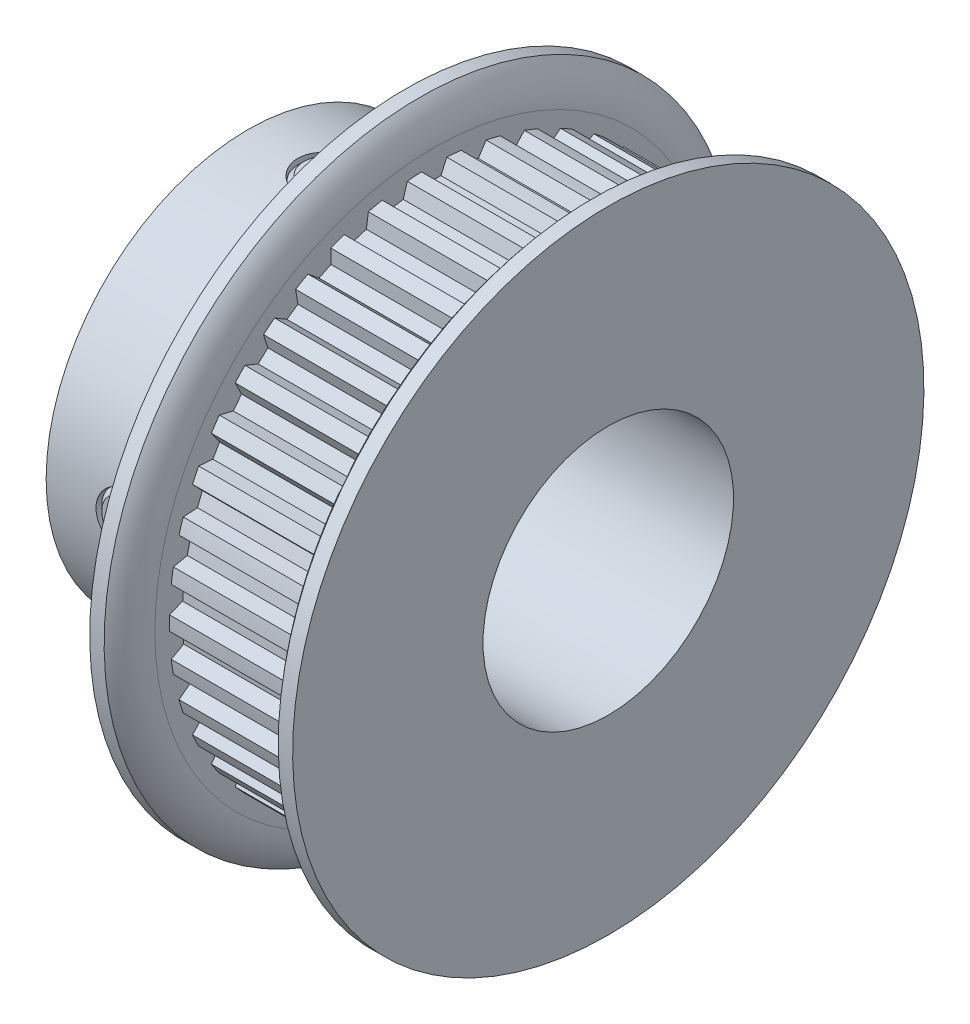
SolidWorks part; units mm, degrees
ref_plane "Front Plane" through (0, 0, 0) normal (0, 0, 1) x (1, 0, 0)
ref_plane "Top Plane" through (0, 0, 0) normal (0, 1, 0) x (1, 0, 0)
ref_plane "Right Plane" through (0, 0, 0) normal (1, 0, 0) x (0, 0, -1)
sketch "Sketch2" plane through (0, 0, 0) normal (1, 0, 0) x (0, 0, -1)
  line L3 (0, 0) -> (0, 12.7635) construction
  line L6 (0, -13.2715) -> (0, -13.589) construction
  line L7 (-0.5715, 13.2592) -> (-0.3383, 12.759)
  line L8 (0.5715, 13.2592) -> (0.3383, 12.759)
  line L9 (-0.5715, 13.2592) -> (-0.6441, 13.4148)
  line L10 (0.5715, 13.2592) -> (0.6441, 13.4148)
  line L12 (-0.3383, 12.759) -> (0.3383, 12.759)
  line L14 (0, 13.2715) -> (0, 13.589) construction
  line L15 (0, 0) -> (0, -1.143) construction
  circle A0 centre (0, 0) radius 13.589 construction
  circle A1 centre (0, 0) radius 12.7635 construction
  circle A2 centre (0, 0) radius 13.2715 construction
  arc A7 (0.6441, 13.4148) -> (-0.6441, 13.4148) centre (0, 0) ccw
  point P5 (0, 13.4303)
  dimension "D3" = 0.3175
  dimension "D1" = 50
sketch "Sketch1" plane through (0, 0, 0) normal (0, 0, 1) x (1, 0, 0)
  line L0 (-9.1313, 0) -> (9.1313, 0) construction
  line L1 (-9.1313, 6.35) -> (9.1313, 6.35)
  line L2 (-9.1313, 6.35) -> (-9.1313, 10.2362)
  line L3 (-1.1557, 16.002) -> (-0.4254, 16.002)
  line L4 (0.3048, 13.589) -> (0.3048, 14.1605)
  line L5 (0.3048, 14.732) -> (0.3048, 13.589) construction
  line L6 (0.3048, 13.589) -> (7.6708, 13.589)
  line L7 (7.6708, 13.589) -> (7.6708, 14.1605)
  line L8 (7.6708, 13.589) -> (9.1313, 13.589) construction
  line L9 (8.4011, 16.002) -> (9.1313, 16.002)
  line L10 (9.1313, 16.002) -> (9.1313, 6.35)
  line L11 (8.4011, 13.589) -> (8.4011, 16.002) construction
  line L12 (-5.1435, 10.2362) -> (-5.1435, 6.35) construction
  line L13 (-1.1557, 16.002) -> (-1.1557, 10.2362)
  line L14 (-1.1557, 10.2362) -> (-9.1313, 10.2362)
  arc A0 (7.6708, 14.1605) -> (8.4011, 16.002) centre (10.3578, 14.1605) cw
  arc A1 (0.3048, 14.1605) -> (-0.4254, 16.002) centre (-2.3822, 14.1605) ccw
  dimension "Bore Size" = 12.7
  dimension "Overall Width" = 18.2626
  dimension "Inside Width" = 7.366
  dimension "OD" = 32.004
  dimension "D2" = 27.178
  dimension "D3" = 1.143
  dimension "D4" = 0.5715
  dimension "Outside Width" = 10.287
revolve "Revolve1" add sketch "Sketch1" angle 360 mid plane about L0
sketch "Sketch4" plane through (0.3048, 0, 0) normal (1, 0, 0) x (0, 0, -1)
  circle A0 centre (0, 0) radius 13.4303
  circle A2 centre (0, 0) radius 13.589
  circle A3 centre (0, 0) radius 13.589 construction
extrude "Cut-Extrude2" cut sketch "Sketch4" along normal up to surface (7.366 mm away) up to face at (7.6708, -13.589, 0)
sketch "Sketch3" plane through (0.3048, 0, 0) normal (1, 0, 0) x (0, 0, -1)
  line L2 (-0.5715, 13.2592) -> (-0.3383, 12.759) construction
  line L3 (-0.3383, 12.759) -> (0.3383, 12.759) construction
  line L4 (0.5715, 13.2592) -> (0.3383, 12.759) construction
  line L5 (-0.6441, 13.4148) -> (-0.3383, 12.759)
  line L6 (-0.3383, 12.759) -> (0.3383, 12.759)
  line L7 (0.6441, 13.4148) -> (0.3383, 12.759)
  arc A1 (0.6441, 13.4148) -> (-0.6441, 13.4148) centre (0, 0) ccw construction
  arc A2 (0.6441, 13.4148) -> (-0.6441, 13.4148) centre (0, 0) ccw
extrude "Cut-Extrude1" cut sketch "Sketch3" along normal up to surface (7.366 mm away) up to face at (7.6708, -14.1605, 0)
pattern_circular "CirPattern1" count 42 over 360 of "Cut-Extrude1"
sketch "Sketch5" plane through (0, 0, 0) normal (0, 0, 1) x (1, 0, 0)
  line L1 (7.6708, 14.1605) -> (7.6708, -14.1605) construction
  point P0 (7.6708, 0)
sketch "Sketch6" plane through (0, 0, 0) normal (0, 1, 0) x (1, 0, 0)
  line L0 (-9.1313, 0) -> (-6.604, 0) construction
  line L1 (-9.1313, 16.002) -> (-9.1313, -16.002) construction
  line L2 (-1.1557, 0) -> (-3.683, 0) construction
  line L4 (-1.1557, 16.002) -> (-1.1557, -16.002) construction
  circle A0 centre (-5.1435, 0) radius 1.4605
  dimension "D1" = 2.921
extrude "Cut-Extrude3" cut sketch "Sketch6" along normal through all
sketch "Sketch7" plane through (0, 0, 0) normal (0, 0, 1) x (1, 0, 0)
  line L0 (-6.3119, 10.2362) -> (-5.1435, 10.2362)
  line L1 (-6.5659, 9.9822) -> (-6.5659, 6.985)
  line L2 (-6.5659, 6.985) -> (-6.3119, 6.731)
  line L3 (-6.3119, 6.731) -> (-5.1435, 6.731)
  line L4 (-5.1435, 6.731) -> (-5.1435, 10.2362) construction
  line L5 (-1.1557, 10.2362) -> (-9.1313, 10.2362) construction
  line L6 (-6.5659, 9.9822) -> (-6.3119, 10.2362)
  line L8 (-5.1435, 10.2362) -> (-5.1435, 6.731)
  point P0 (-6.5659, 10.2362)
  point P4 (-6.5659, 6.731)
  dimension "D1" = 2.8448
  dimension "D2" = 0.381
revolve "Revolve2" add sketch "Sketch7" angle 360 mid plane about L4
sketch "Sketch8" plane through (0, 10.2362, 0) normal (0, 1, 0) x (1, 0, 0)
  line L1 (-5.1435, 0.8212) -> (-5.8547, 0.4106)
  line L2 (-5.8547, 0.4106) -> (-5.8547, -0.4106)
  line L3 (-5.8547, -0.4106) -> (-5.1435, -0.8212)
  line L4 (-5.1435, -0.8212) -> (-4.4323, -0.4106)
  line L5 (-4.4323, -0.4106) -> (-4.4323, 0.4106)
  line L6 (-4.4323, 0.4106) -> (-5.1435, 0.8212)
  circle A0 centre (-5.1435, 0) radius 0.7112 construction
  dimension "D1" = 1.4224
extrude "Cut-Extrude4" cut sketch "Sketch8" against normal blind 1.016
pattern_circular "CirPattern2" count 2 over 90 about axis through (-9.1313, 0, 0) along (-1, 0, 0) of "Cut-Extrude3" reverse direction yes
pattern_circular "CirPattern3" count 2 over 90 reverse direction yes of bodies 107
sketch "Sketch9" plane through (-9.1313, 0, 0) normal (-1, 0, 0) x (0, 0, 1)
  circle A0 centre (0, 0) radius 6.35
extrude "Cut-Extrude5" cut sketch "Sketch9" against normal through all rebuild error yes
equation "\"D3@Sketch2\" = (\"hs@Sketch2\"-\"ht@Sketch2\")/2"
equation "\"D2@Sketch1\" = \"PD@Sketch2\""
equation "\"D3@Sketch1\" = \"hs@Sketch2\""
equation "\"D4@Sketch1\" = \"D3@Sketch1\"/2"
